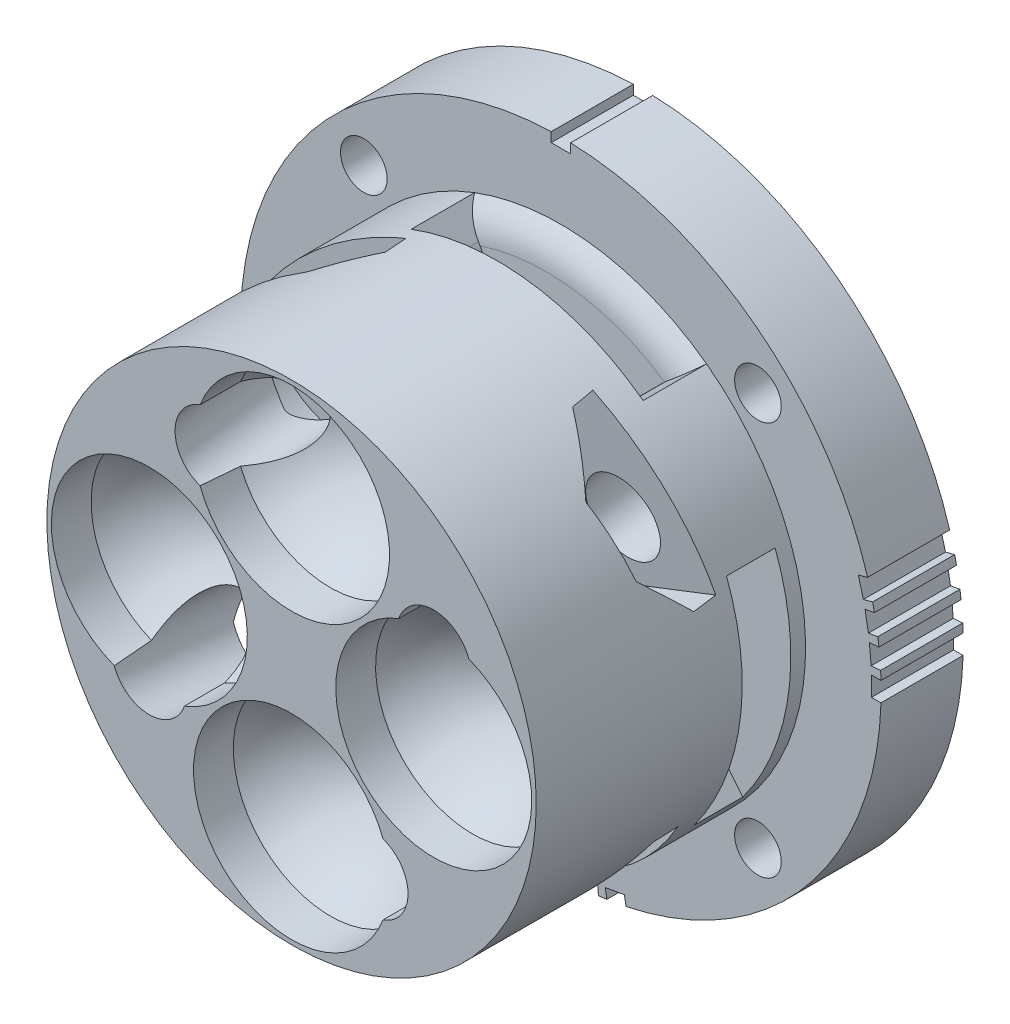
SolidWorks part; units mm, degrees
other "Camera1"
material "Custom Plastic"
ref_plane "Front Plane" through (0, 0, 0) normal (0, 0, 1) x (1, 0, 0)
ref_plane "Top Plane" through (0, 0, 0) normal (0, 1, 0) x (1, 0, 0)
ref_plane "Right Plane" through (0, 0, 0) normal (1, 0, 0) x (0, 0, -1)
sketch "Sketch1" plane through (0, 0, 0) normal (0, 0, 1) x (1, 0, 0)
  circle A0 centre (0, 0) radius 24.765
  dimension "D1" = 49.53
extrude "Base" add sketch "Sketch1" along normal blind 6.35
sketch "Sketch2" plane through (0, 0, 6.35) normal (0, 0, 1) x (1, 0, 0)
  circle A0 centre (0, 0) radius 18.923
  dimension "D1" = 37.846
extrude "Barrel" add sketch "Sketch2" along normal blind 20.828
ref_point "Origin Point"
ref_axis "Central Axis" through (0, 0, -48.9443) along (0, 0, 1)
sketch "Sketch3" plane through (0, 0, 6.35) normal (0, 0, 1) x (1, 0, 0)
  circle A0 centre (15.24, -15.24) radius 1.8034
  dimension "D1" = 3.6068
  dimension "D2" = 15.24
  dimension "D3" = 15.24
extrude "Screw Hole Ref" cut sketch "Sketch3" against normal through all
pattern_circular "Screw Hole Pattern" count 4 over 360 about axis through (0, 0, -48.9443) along (0, 0, 1) of "Screw Hole Ref"
sketch "Sketch4" plane through (0, 0, 27.178) normal (0, 0, 1) x (1, 0, 0)
  circle A0 centre (0, 10.9982) radius 2.5797
  dimension "D1" = 5.1594
  dimension "D2" = 10.9982
extrude "Photodiode Hole Ref" cut sketch "Sketch4" against normal through all
ref_axis "Photodiode Ref Axis" through (0, 10.9982, 0) along (0, 0, 1)
ref_plane "Photodiode Radial Plane" through (0, 0, 0) normal (-1, 0, 0) x (0, 0, 1)
ref_plane "Photodiode Tangential Plane" through (0, 10.9982, 0) normal (0, -1, 0) x (0, 0, 1)
sketch "Sketch5" plane through (0, 10.9982, 0) normal (0, -1, 0) x (0, 0, 1)
  line L0 (0, 0) -> (27.178, 0) construction
  line L14 (0, -27.229) -> (0, 27.229) construction
  line L16 (0, 0) -> (2.5294, 0)
  line L17 (0, 0) -> (0, -5.2145)
  line L18 (0, -5.2145) -> (2.5294, -5.2145)
  line L19 (24.1734, -7.506) -> (27.178, -7.5784)
  line L20 (27.178, 0) -> (24.1734, 0)
  line L21 (27.178, 0) -> (27.178, -7.506)
  line L22 (2.5294, 0) -> (24.1734, 0)
  line L23 (7.1392, -2.5305) -> (19.2088, -2.5305)
  line L24 (27.178, -7.5784) -> (27.178, -7.506)
  arc A2 (24.1734, -7.506) -> (19.2088, -2.5305) centre (28.4522, 1.7281) cw
  arc A3 (2.5294, -5.2145) -> (7.1392, -2.5305) centre (2.5294, 0.0863) ccw
  point P11 (1.6914, -0.9202)
  point P12 (18.3703, -3.537)
  point P13 (28.4522, 1.7281)
  point P26 (0, 13.847)
  dimension "D7" = 10.1773
  dimension "D10" = 5.3007
  dimension "D1" = 21.644
  dimension "D2" = 2.5294
  dimension "D3" = 3.0046
  dimension "D4" = 7.506
  dimension "D5" = 3.0046
  dimension "D6" = 7.506
  dimension "D8" = 9.2341
  dimension "D9" = 2.5305
  dimension "D11" = 2.5294
  dimension "D12" = 5.2145
  dimension "D13" = 0.0863
  dimension "D14" = 2.5294
  dimension "D15" = 0
  dimension "D16" = 0
revolve "Photodiode Ref Lens Cut" cut sketch "Sketch5" angle 360 about axis through (0, 10.9982, 0) along (0, 0, 1)
sketch "Photodiode Filter Cut Sketch" plane through (0, 10.9982, 0) normal (0, -1, 0) x (0, 0, 1)
  line L0 (19.2316, 2.54) -> (7.1109, 2.54) construction
  line L4 (7.4919, -7.9867) -> (7.4919, 4.74)
  line L5 (19.2316, -2.5797) -> (19.2316, 2.5797) construction
  line L6 (7.1109, 2.5797) -> (7.1109, -2.5797) construction
  dimension "D1" = 12.7267
  dimension "D2" = 2.2
  dimension "D3" = 0.381
ref_plane "Photodiode Filter Cutting Plane" through (0, 0, 7.4919) normal (0, 0, 1) x (-1, 0, 0)
sketch "Sketch12" plane through (0, 0, 7.4919) normal (0, 0, 1) x (-1, 0, 0)
  line L0 (0, 0) -> (-4.113, -29.4712) construction
  line L2 (-7.9889, -10.9409) -> (4.6882, -12.7101) construction
  line L4 (-7.9889, -10.9409) -> (-9.9972, -25.3312)
  line L5 (4.6882, -12.7101) -> (2.6799, -27.1004)
  line L6 (2.6799, -27.1004) -> (-9.9972, -25.3312)
  circle A1 centre (0, -10.9982) radius 2.54 construction
  arc A2 (4.6882, -12.7101) -> (-7.9889, -10.9409) centre (-1.6504, -11.8255) ccw construction
  circle A3 centre (-1.6504, -11.8255) radius 4.345 construction
  arc A4 (4.6882, -12.7101) -> (-7.9889, -10.9409) centre (-1.6504, -11.8255) ccw
  arc A5 (-7.9889, -10.9409) -> (4.6882, -12.7101) centre (-1.6504, -11.8255) ccw construction
  point P5 (-1.6504, -11.8255)
  point P10 (-1.6504, -11.8255)
  dimension "D1" = 12.8
  dimension "D6" = 5.08
  dimension "D3" = 8.69
  dimension "D2" = 12.8
extrude "Photodiode Filter Cut Ref" cut sketch "Sketch12" along normal blind 3.7592
chamfer "Photodiode Filter Access Cut" distance 3 distance2 4 2 edges at (-3.8772, 18.5215, 9.3715) (8.8, 16.7523, 9.3715) first distance on face at (2.5385, 18.1891, 9.3715)
fillet "Fillet5" radius 3.54 2 edges at (8.2471, 12.7907, 9.3715) (-4.43, 14.5599, 9.3715)
fillet "Fillet8" radius 3.54 1 edges at (2.6155, 18.7414, 7.4919)
sketch "LED Cut Constr. Base Point" plane through (0, 0, 0) normal (0, 0, -1) x (-1, 0, 0)
  line L0 (-17.7883, 10.9982) -> (17.7883, 10.9982) construction
  point P0 (9.4489, 10.9982)
  dimension "D1" = 9.4489
sketch "LED Cut Sketch" plane through (0, 10.9982, 0) normal (0, -1, 0) x (0, 0, 1)
  line L0 (0, 9.4489) -> (48.7524, 3.4628) construction
  line L1 (0, -27.2415) -> (0, 27.2415) construction
  line L2 (24.1734, -7.506) -> (24.1734, 7.506) construction
  line L4 (29.6565, 8.7041) -> (29.3061, 5.8505)
  line L5 (29.3061, 5.8505) -> (0, 9.4489)
  line L6 (0, 9.4489) -> (-3.6946, 9.9025)
  line L7 (-3.6946, 9.9025) -> (-3.3443, 12.7561)
  line L14 (-3.3443, 12.7561) -> (29.6565, 8.7041)
  point P3 (24.1734, 7.506)
  point P7 (24.1734, 7.506)
  dimension "D1" = 2.875
  dimension "D2" = 33.2486
  dimension "D3" = 83
revolve "LED Cut Ref" cut sketch "LED Cut Sketch" angle 360 about L0
sketch "LED Filter Cut Sketch" plane through (0, 10.9982, 0) normal (0, -1, 0) x (0, 0, 1)
  line L0 (12.9031, 10.8871) -> (12.0377, 3.8393)
  line L2 (27.178, 9.1344) -> (0, 12.4714) construction
  line L3 (27.178, -18.923) -> (27.178, 18.923) construction
  line L4 (27.178, 7.077) -> (27.178, 9.0084) construction
  line L5 (0, -27.2415) -> (0, 27.2415) construction
  line L6 (0, 12.3455) -> (0, 6.5523) construction
  dimension "D1" = 13
ref_plane "LED Filter Cutting Plane" through (1.3991, 0, 11.3945) normal (-0.1219, 0, -0.9925) x (0.9925, 0, -0.1219)
ref_plane "LED Filter Cut-view Plane" through (1.3991, 0, 11.3945) normal (0.1219, 0, 0.9925) x (-0.9925, 0, 0.1219)
sketch "Sketch10" plane through (1.3991, 0, 11.3945) normal (-0.1219, 0, -0.9925) x (0.9925, 0, -0.1219)
  line L5 (-10.5659, -8.9005) -> (-15.7459, -21.1494) construction
  line L6 (-4.7174, -11.3739) -> (-16.4144, -6.4272) construction
  line L7 (-4.7174, -11.3739) -> (-11.2179, -26.7452)
  line L8 (-16.4144, -6.4272) -> (-22.9149, -21.7985)
  line L9 (-11.2179, -26.7452) -> (-22.9149, -21.7985)
  arc A1 (-4.7174, -11.3739) -> (-16.4144, -6.4272) centre (-10.5659, -8.9005) ccw construction
  circle A2 centre (-10.5659, -8.9005) radius 5.6007 construction
  arc A3 (-4.7174, -11.3739) -> (-16.4144, -6.4272) centre (-10.5659, -8.9005) ccw
  arc A4 (-4.7174, -11.3739) -> (-16.4144, -6.4272) centre (-10.5659, -8.9005) cw construction
  point P8 (-10.5659, -8.9005)
  dimension "D2" = 12.7
  dimension "D3" = 11.2014
extrude "LED Filter Cut Ref" cut sketch "Sketch10" against normal blind 1.778
ref_axis "Axis1" through (-9.088, 8.9005, 12.6822) along (0.1219, 0, 0.9925)
ref_plane "Plane2" through (-4.7602, 11.3406, 0.5845) normal (0.3866, -0.921, -0.0475) x (-0.9222, -0.3861, -0.0204)
ref_plane "Plane3" through (1.6158, 0, 13.1593) normal (-0.1219, 0, -0.9925) x (-0.9925, 0, 0.1219)
sketch "Sketch15" plane through (1.6158, 0, 13.1593) normal (-0.1219, 0, -0.9925) x (-0.9925, 0, 0.1219)
  line L0 (22.9149, 21.7985) -> (16.4144, 6.4272)
  line L1 (4.7174, 11.3739) -> (11.2179, 26.7452)
  line L2 (11.2179, 26.7452) -> (22.9149, 21.7985)
  arc A0 (4.7174, 11.3739) -> (16.4144, 6.4272) centre (10.5659, 8.9005) ccw
sketch "Sketch16" plane through (-4.7602, 11.3406, 0.5845) normal (0.3866, -0.921, -0.0475) x (-0.9222, -0.3861, -0.0204)
  line L0 (4.6869, -12.2095) -> (3.789, -18.9202) construction
  line L1 (-1.8428, -13.1297) -> (10.745, -14.8139) construction
  point P0 (3.788, -18.9276)
  dimension "D1" = 5
loft "Cut-Loft1" cut profiles "Sketch15", "Sketch16"
fillet "Fillet11" radius 1 2 edges
pattern_circular "Cut Pattern" count 4 over 360 about axis through (0, 0, -48.9443) along (0, 0, 1) of "Photodiode Hole Ref", "Photodiode Ref Lens Cut", "LED Cut Ref", "LED Filter Cut Ref", "Photodiode Filter Cut Ref", "Photodiode Filter Access Cut", "Cut-Loft1"
sketch "Sketch13" plane through (0, 0, 0) normal (0, 0, -1) x (-1, 0, 0)
  line L0 (0, 0) -> (0, 10.9982) construction
  line L1 (0, 10.9982) -> (0, 24.765) construction
  line L2 (0, 0) -> (0, -24.765) construction
  line L3 (-24.765, 0) -> (24.765, 0) construction
  line L4 (24.015, 0.75) -> (24.015, -0.75)
  line L5 (-0.75, 24.015) -> (0.75, 24.015)
  line L6 (-0.75, 24.015) -> (-0.75, 25.515)
  line L7 (-0.75, 25.515) -> (0.75, 25.515)
  line L8 (0.75, 24.015) -> (0.75, 25.515)
  line L9 (-0.75, 24.015) -> (0.75, 25.515) construction
  line L10 (-0.75, 25.515) -> (0.75, 24.015) construction
  line L11 (24.015, 0.75) -> (25.515, 0.75)
  line L12 (25.515, 0.75) -> (25.515, -0.75)
  line L13 (24.015, -0.75) -> (25.515, -0.75)
  line L14 (24.015, 0.75) -> (25.515, -0.75) construction
  line L15 (25.515, 0.75) -> (24.015, -0.75) construction
  line L16 (0.75, -24.015) -> (-0.75, -24.015)
  line L17 (0.75, -24.015) -> (0.75, -25.515)
  line L18 (0.75, -25.515) -> (-0.75, -25.515)
  line L19 (-0.75, -24.015) -> (-0.75, -25.515)
  line L20 (0.75, -24.015) -> (-0.75, -25.515) construction
  line L21 (0.75, -25.515) -> (-0.75, -24.015) construction
  line L22 (-24.015, -0.75) -> (-24.015, 0.75)
  line L23 (-24.015, -0.75) -> (-25.515, -0.75)
  line L24 (-25.515, -0.75) -> (-25.515, 0.75)
  line L25 (-24.015, 0.75) -> (-25.515, 0.75)
  line L26 (-24.015, -0.75) -> (-25.515, 0.75) construction
  line L27 (-25.515, -0.75) -> (-24.015, 0.75) construction
  line L28 (0, 0) -> (0.75, 24.015) construction
  line L29 (0, 0) -> (24.015, -0.75) construction
  line L30 (23.989, -1.3459) -> (23.8582, -2.8402)
  line L31 (23.989, -1.3459) -> (25.4833, -1.4766)
  line L32 (25.4833, -1.4766) -> (25.3525, -2.9709)
  line L33 (23.8582, -2.8402) -> (25.3525, -2.9709)
  line L34 (-24.6708, 2.1584) -> (24.6708, -2.1584) construction
  line L35 (23.989, -1.3459) -> (25.3525, -2.9709) construction
  line L36 (25.4833, -1.4766) -> (23.8582, -2.8402) construction
  line L37 (0, 0) -> (23.8582, -2.8402) construction
  line L38 (-1.3459, -23.989) -> (-2.8402, -23.8582)
  line L39 (-1.3459, -23.989) -> (-1.4766, -25.4833)
  line L40 (-1.4766, -25.4833) -> (-2.9709, -25.3525)
  line L41 (-2.8402, -23.8582) -> (-2.9709, -25.3525)
  line L42 (-3.4316, -23.7804) -> (-4.9088, -23.5199)
  line L43 (-3.4316, -23.7804) -> (-3.692, -25.2576)
  line L44 (-3.692, -25.2576) -> (-5.1692, -24.9971)
  line L45 (-4.9088, -23.5199) -> (-5.1692, -24.9971)
  line L46 (2.1584, 24.6708) -> (-2.1584, -24.6708) construction
  line L47 (-1.3459, -23.989) -> (-2.9709, -25.3525) construction
  line L48 (-1.4766, -25.4833) -> (-2.8402, -23.8582) construction
  line L49 (0, 0) -> (-2.8402, -23.8582) construction
  line L50 (4.3004, 24.3888) -> (-4.3004, -24.3888) construction
  line L51 (-3.4316, -23.7804) -> (-5.1692, -24.9971) construction
  line L52 (-3.692, -25.2576) -> (-4.9088, -23.5199) construction
  line L53 (0, 0) -> (-4.9088, -23.5199) construction
  line L54 (0, 0) -> (23.8582, -2.8402) construction
  line L55 (0, 0) -> (-4.9088, -23.5199) construction
  line L56 (-23.989, 1.3459) -> (-23.8582, 2.8402)
  line L57 (-23.989, 1.3459) -> (-25.4833, 1.4766)
  line L58 (-25.4833, 1.4766) -> (-25.3525, 2.9709)
  line L59 (-23.8582, 2.8402) -> (-25.3525, 2.9709)
  line L60 (-23.7804, 3.4316) -> (-23.5199, 4.9088)
  line L61 (-23.7804, 3.4316) -> (-25.2576, 3.692)
  line L62 (-25.2576, 3.692) -> (-24.9971, 5.1692)
  line L63 (-23.5199, 4.9088) -> (-24.9971, 5.1692)
  line L64 (-23.3908, 5.4911) -> (-23.0026, 6.94)
  line L65 (-23.3908, 5.4911) -> (-24.8397, 5.8793)
  line L66 (-24.8397, 5.8793) -> (-24.4515, 7.3282)
  line L67 (-23.0026, 6.94) -> (-24.4515, 7.3282)
  line L68 (0, 0) -> (-24.6708, 2.1584) construction
  line L69 (-23.989, 1.3459) -> (-25.3525, 2.9709) construction
  line L70 (-25.4833, 1.4766) -> (-23.8582, 2.8402) construction
  line L71 (24.3888, -4.3004) -> (-24.3888, 4.3004) construction
  line L72 (-23.7804, 3.4316) -> (-24.9971, 5.1692) construction
  line L73 (-25.2576, 3.692) -> (-23.5199, 4.9088) construction
  line L74 (0, 0) -> (-23.5199, 4.9088) construction
  line L75 (23.9212, -6.4097) -> (-23.9212, 6.4097) construction
  line L76 (-23.3908, 5.4911) -> (-24.4515, 7.3282) construction
  line L77 (-24.8397, 5.8793) -> (-23.0026, 6.94) construction
  line L78 (0, 0) -> (-23.0026, 6.94) construction
  line L79 (0, 0) -> (-23.0026, 6.94) construction
  line L80 (0, 0) -> (-0.75, -24.015) construction
  line L81 (0, 0) -> (-23.8582, 2.8402) construction
  circle A0 centre (0, 0) radius 24.765 construction
  point P0 (0, 0)
  point P13 (0, 0)
  point P42 (0, 0)
  dimension "D1" = 1.5
  dimension "D2" = 1.5
  dimension "D4" = 24.0267
extrude "Channel Markers" cut sketch "Sketch13" against normal through all
